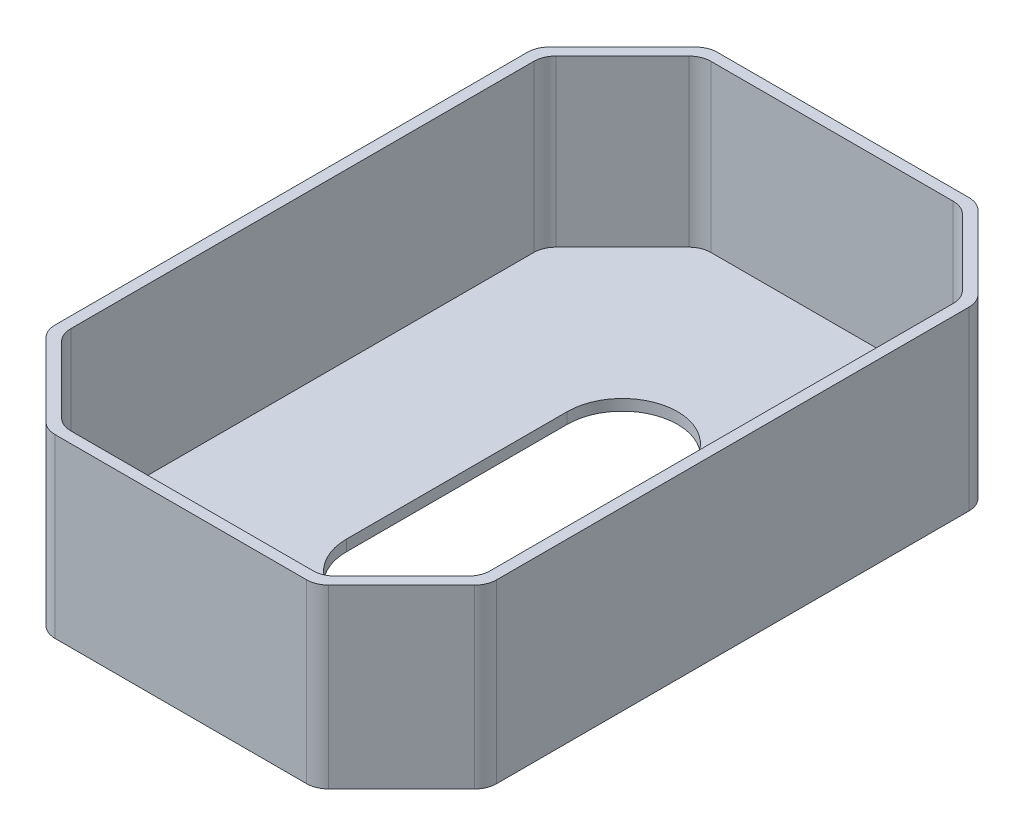
SolidWorks part; units mm, degrees
ref_plane "Front Plane" through (0, 0, 0) normal (0, 0, 1) x (1, 0, 0)
ref_plane "Top Plane" through (0, 0, 0) normal (0, 1, 0) x (1, 0, 0)
ref_plane "Right Plane" through (0, 0, 0) normal (1, 0, 0) x (0, 0, -1)
sketch "Sketch1" plane through (0, 0, 0) normal (0, 1, 0) x (1, 0, 0)
  line L0 (0, -190.5) -> (0, 190.5) construction
  line L1 (-127, 0) -> (127, 0) construction
  line L2 (-127, 141.1086) -> (-77.6086, 190.5)
  line L3 (-77.6086, -190.5) -> (77.6086, -190.5)
  line L4 (-127, -141.1086) -> (-127, 141.1086)
  line L5 (-77.6086, 190.5) -> (77.6086, 190.5)
  line L6 (127, -141.1086) -> (127, 141.1086)
  line L7 (-127, -141.1086) -> (127, 141.1086) construction
  line L8 (-127, 141.1086) -> (127, -141.1086) construction
  line L9 (-127, -141.1086) -> (-77.6086, -190.5)
  line L10 (127, -141.1086) -> (77.6086, -190.5)
  line L11 (127, 141.1086) -> (77.6086, 190.5)
  line L12 (-74.9783, 184.15) -> (74.9783, 184.15)
  line L13 (120.65, 138.4783) -> (74.9783, 184.15)
  line L14 (120.65, -138.4783) -> (120.65, 138.4783)
  line L15 (120.65, -138.4783) -> (74.9783, -184.15)
  line L16 (-74.9783, -184.15) -> (74.9783, -184.15)
  line L17 (-120.65, -138.4783) -> (-74.9783, -184.15)
  line L18 (-120.65, -138.4783) -> (-120.65, 138.4783)
  line L19 (-120.65, 138.4783) -> (-74.9783, 184.15)
  line L20 (0, -63.5) -> (0, 63.5) construction
  line L21 (-31.75, 63.5) -> (-31.75, -63.5)
  line L22 (31.75, 63.5) -> (31.75, -63.5)
  arc A0 (31.75, 63.5) -> (-31.75, 63.5) centre (0, 63.5) ccw
  arc A1 (-31.75, -63.5) -> (31.75, -63.5) centre (0, -63.5) ccw
  point P0 (0, 0)
  point P4 (0, 0)
  point P8 (0, 0)
  point P32 (0, 0)
  dimension "D9" = 63.5
  dimension "D1" = 381
  dimension "D2" = 254
  dimension "D3" = 69.85
  dimension "D4" = 45
  dimension "D5" = 69.85
  dimension "D6" = 45
  dimension "D7" = 6.35
  dimension "D8" = 127
extrude "Boss-Extrude1" add sketch "Sketch1" along normal blind 6.35 contours L19 L18 L17 L16 L15 L14 L13 L12 A1 L21 A0 L22 | L6 L11 L5 L2 L4 L9 L3 L10 L18 L19 L12 L13 L14 L15 L16 L17 region at (-99.0664, 0, -162.5664) region at (0, 0, -179.7469)
extrude "Boss-Extrude2" add sketch "Sketch1<4>" along normal blind 101.6 contours L6 L11 L5 L2 L4 L9 L3 L10 L18 L19 L12 L13 L14 L15 L16 L17 region at (-99.0664, 0, -162.5664)
sketch "Sketch1<4>" plane through (0, 0, 0) normal (0, 1, 0) x (1, 0, 0) same geometry as "Sketch1"
fillet "Fillet1" radius 12.7 8 edges at (77.6086, 50.8, 190.5) (127, 50.8, 141.1086) (-77.6086, 50.8, 190.5) (-127, 50.8, 141.1086) (-127, 50.8, -141.1086) (-77.6086, 50.8, -190.5) (127, 50.8, -141.1086) (77.6086, 50.8, -190.5)
fillet "Fillet2" radius 12.7 8 edges at (74.9783, 53.975, 184.15) (120.65, 53.975, 138.4783) (-74.9783, 53.975, 184.15) (-120.65, 53.975, 138.4783) (-120.65, 53.975, -138.4783) (120.65, 53.975, -138.4783) (74.9783, 53.975, -184.15) (-74.9783, 53.975, -184.15)
sketch "Sketch3" plane through (0, 0, 190.5) normal (0, 0, 1) x (1, 0, 0)
  line L0 (-68.4276, 69.2994) -> (31.2922, 69.2994)
  line L1 (-65.9408, 29.6375) -> (26.9262, 29.6375)
  line L2 (-88.3365, 49.3905) -> (51.3635, 49.2282) construction
  arc A0 (-68.4276, 69.2994) -> (-65.9408, 29.6375) centre (-68.4276, 49.3905) ccw
  arc A1 (31.2922, 69.2994) -> (26.9262, 29.6375) centre (31.2922, 49.2282) cw
  dimension "D1" = 139.7
